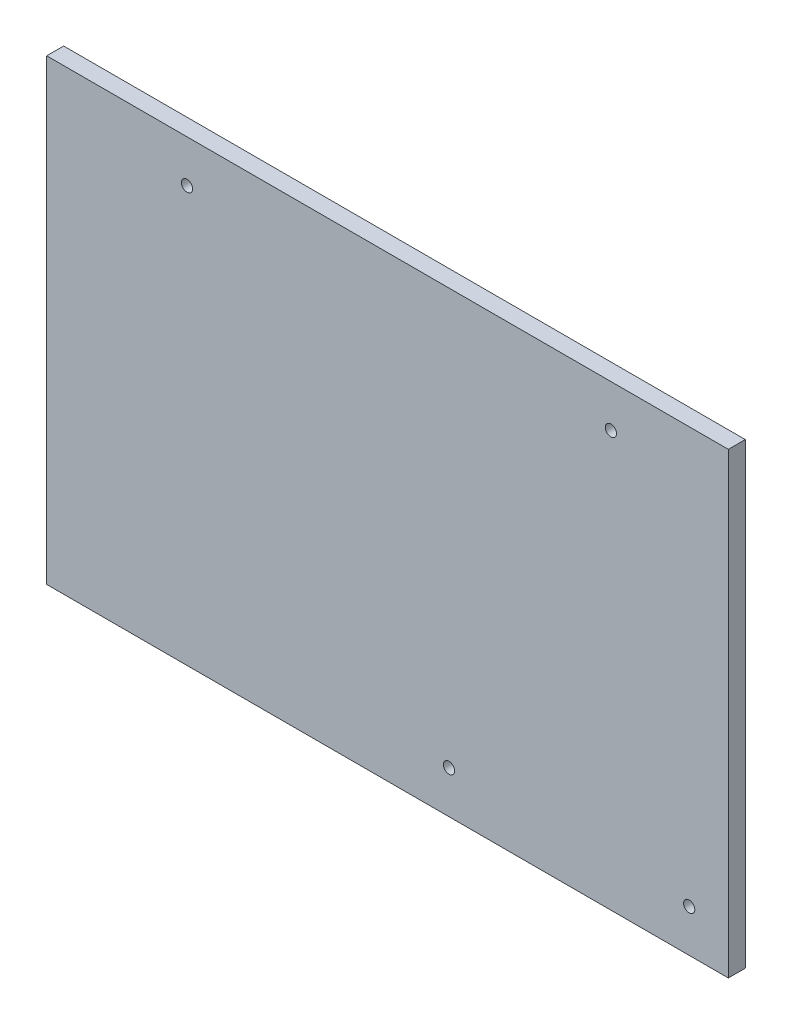
SolidWorks part; units mm, degrees
ref_plane "Front Plane" through (0, 0, 0) normal (0, 0, 1) x (1, 0, 0)
ref_plane "Top Plane" through (0, 0, 0) normal (0, 1, 0) x (1, 0, 0)
ref_plane "Right Plane" through (0, 0, 0) normal (1, 0, 0) x (0, 0, -1)
sketch "Sketch1" plane through (0, 0, 0) normal (0, 0, 1) x (1, 0, 0)
  line L0 (115.91, -3.175) -> (115.91, 3.175) construction
  line L1 (115.91, -15.875) -> (-139.3499, -15.875)
  line L2 (115.91, -15.875) -> (115.91, 155.575)
  line L3 (115.91, 155.575) -> (-139.3499, 155.575)
  line L4 (-139.3499, -15.875) -> (-139.3499, 155.575)
  line L5 (113.7824, 69.85) -> (-193.0608, 69.85) construction
  line L6 (115.91, -3.175) -> (103.3828, -3.175) construction
  line L7 (115.91, 142.875) -> (103.6814, 142.875) construction
  ellipse E0 centre (47.625, 171.7384) end of major axis (47.625, -44.1616) minor radius 186.9749 (190.7889, 310.6087) -> (180.097, 324.101) ccw construction
  dimension "D1" = 12.7
extrude "Boss-Extrude1" add sketch "Sketch1" along normal blind 6.35
sketch "Sketch7" plane through (0, 0, 0) normal (0, 0, -1) x (-1, 0, 0)
  line L0 (-13.426, 3.175) -> (-9.1588, -3.175) construction
  line L1 (-9.1588, 3.175) -> (-13.426, -3.175) construction
  line L2 (-103.3828, 3.175) -> (-99.1156, -3.175) construction
  line L3 (-103.3828, -3.175) -> (-99.1156, 3.175) construction
  line L4 (-74.065, 136.525) -> (-69.7978, 142.875) construction
  line L5 (-69.7978, 136.525) -> (-74.065, 142.875) construction
  line L6 (84.685, 136.525) -> (88.9522, 142.875) construction
  line L7 (88.9522, 136.525) -> (84.685, 142.875) construction
  circle A0 centre (-11.2924, 0) radius 2.0955
  circle A1 centre (-101.2492, 0) radius 2.0955
  circle A2 centre (-71.9314, 139.7) radius 2.0955
  circle A3 centre (86.8186, 139.7) radius 2.0955
  dimension "D1" = 4.191
extrude "Cut-Extrude4" cut sketch "Sketch7" against normal through all
